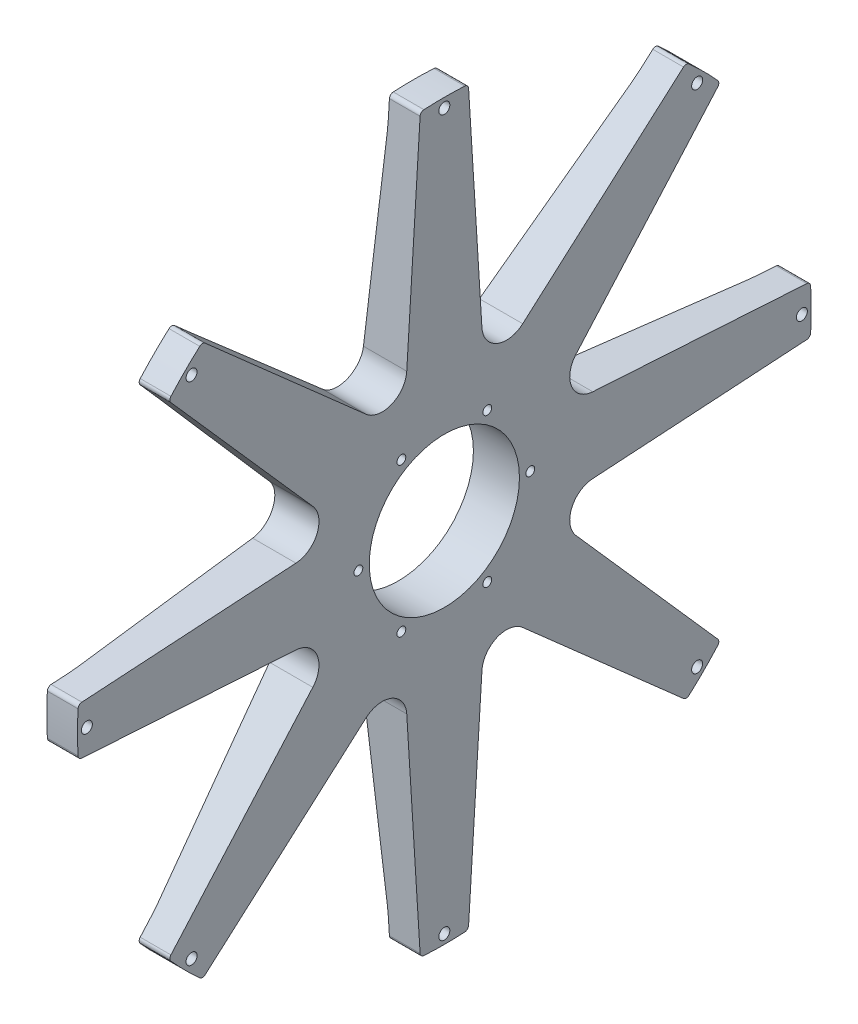
SolidWorks part; units mm, degrees
material "6061-T6 (SS)"
ref_plane "Front Plane" through (0, 0, 0) normal (1, 0, 0) x (0, 1, 0)
ref_plane "Top Plane" through (0, 0, 0) normal (0, 0, 1) x (0, 1, 0)
ref_plane "Right Plane" through (0, 0, 0) normal (0, 1, 0) x (-1, 0, 0)
sketch "Rim Base" plane through (1321.9127, 0, 0) normal (-1, 0, 0) x (0, -1, 0)
  line L0 (-601.9127, 917.067) -> (-621.8122, 869.0252) construction
  line L1 (-601.9127, 742.367) -> (-601.9127, 737.792)
  line L2 (-601.9127, 737.792) -> (-601.9127, 737.592) construction
  line L3 (-601.9127, 917.067) -> (-582.0132, 869.0252) construction
  line L4 (-601.9127, 917.067) -> (-601.9127, 742.367)
  line L5 (-621.8122, 869.0252) -> (-606.8221, 747.1987)
  line L6 (-601.9127, 742.367) -> (-589.9127, 742.367) construction
  line L7 (-607.2191, 747.1498) -> (-606.8221, 747.1987) construction
  line L8 (-601.9127, 917.067) -> (-601.9127, 969.067)
  line L9 (-590.064, 739.9415) -> (-582.0132, 869.0252)
  line L10 (-582.0132, 869.0252) -> (-587.2177, 738.1946) construction
  circle A0 centre (-601.9127, 742.367) radius 2.6892
  circle A1 centre (-601.9127, 742.367) radius 2.4892 construction
  circle A2 centre (-601.9127, 742.367) radius 4.575
  arc A3 (-616.6077, 738.1946) -> (-587.2177, 738.1946) centre (-601.9127, 917.067) ccw construction
  arc A4 (-616.6077, 738.1946) -> (-587.2177, 738.1946) centre (-601.9127, 917.067) ccw construction
  circle A5 centre (-601.9127, 1091.767) radius 2.4892 construction
  circle A6 centre (-601.9127, 1091.767) radius 2.4892
  circle A7 centre (-601.9127, 917.067) radius 36.7
  circle A8 centre (-601.9127, 917.067) radius 36.5 construction
  circle A9 centre (-601.9127, 917.067) radius 36.5 construction
  circle A10 centre (-601.9127, 917.067) radius 36.5
  circle A11 centre (-601.9127, 917.067) radius 52
  arc A12 (-557.9844, 944.8934) -> (-599.7785, 969.0232) centre (-601.9127, 917.067) ccw construction
  arc A13 (-606.8221, 747.1987) -> (-606.4872, 742.3024) centre (-651.8191, 741.662) cw
  arc A14 (-590.064, 739.9415) -> (-591.9489, 738.0691) centre (-592.0601, 740.066) cw
  arc A15 (-601.9127, 737.792) -> (-591.9489, 738.0691) centre (-601.9127, 917.067) ccw
  circle A16 centre (-638.2858, 938.067) radius 2.1527 construction
  circle A17 centre (-638.2858, 896.067) radius 2.1527 construction
  circle A18 centre (-601.9127, 875.067) radius 2.1526 construction
  circle A19 centre (-565.5396, 896.067) radius 2.1526 construction
  circle A20 centre (-565.5396, 938.067) radius 2.1527 construction
  circle A21 centre (-601.9127, 959.067) radius 2.1526 construction
  circle A22 centre (-638.2858, 938.067) radius 2.1526
  circle A23 centre (-638.2858, 896.067) radius 2.1526
  circle A24 centre (-601.9127, 875.067) radius 2.1526
  circle A25 centre (-565.5396, 896.067) radius 2.1526
  circle A26 centre (-565.5396, 938.067) radius 2.1526
  circle A27 centre (-601.9127, 959.067) radius 2.1526
  arc M9 (-592.0897, 747.351) -> (-611.7357, 747.351) centre (-601.9127, 917.067) cw
  dimension "D1" = 0.2
  dimension "D2" = 0.2
  dimension "D3" = 0.2
  dimension "D4" = 12
  dimension "D7" = 2
  dimension "D5" = 22.5
  dimension "D6" = 0.4
extrude "Boss-Extrude1" add sketch "Rim Base" along normal blind 22.5 contours A11 L4 M9 | L4 A11 L8 A7 | L1 A2 L4 A0 | L4 A2 M9 | L8 A27 | A26 | L4 A24 | A25 region at (1321.9127, 599.9388, 740.3931) region at (1321.9127, 593.7172, 808.6969) region at (1321.9127, 600.7499, 868.9906) region at (1321.9127, 600.9991, 875.067) region at (1321.9127, 600.9991, 959.067) region at (1321.9127, 565.5396, 896.067) region at (1321.9127, 565.5396, 938.067)
ref_axis "Axis1" through (1299.4127, 601.9127, 917.067) along (1, 0, 0)
ref_axis "Axis2" through (1299.4127, 601.9127, 742.367) along (1, 0, 0)
ref_plane "Plane1" through (0, 601.9127, 0) normal (0, 1, 0) x (1, 0, 0)
sketch "Sketch1" plane through (0, 601.9127, 0) normal (0, 1, 0) x (1, 0, 0)
  line L0 (1321.9127, -865.067) -> (1299.4127, -865.067)
  line L1 (1299.4127, -880.367) -> (1299.4127, -745.0562) construction
  line L2 (1299.4127, -880.367) -> (1299.4127, -745.0562)
  line L6 (1299.4127, -739.6778) -> (1299.4127, -745.0562) construction
  line L7 (1306.9127, -737.792) -> (1306.9127, -747.792)
  line L9 (1306.7337, -753.1409) -> (1299.5918, -859.718)
  line L12 (1299.4127, -739.6778) -> (1299.4127, -737.792) construction
  line L13 (1299.4127, -737.792) -> (1321.9127, -737.792) construction
  line L15 (1299.4127, -739.6778) -> (1299.4127, -745.0562)
  line L16 (1299.4127, -739.6778) -> (1299.4127, -737.792)
  line L17 (1299.4127, -737.792) -> (1321.9127, -737.792)
  line L18 (1321.9127, -739.6778) -> (1321.9127, -737.792) construction
  arc A0 (1306.9127, -747.792) -> (1306.7337, -753.1409) centre (1226.9127, -747.792) cw
  arc A1 (1299.5918, -859.718) -> (1299.4127, -865.067) centre (1379.4127, -865.067) ccw
  dimension "D3" = 80
  dimension "D1" = 15
  dimension "D2" = 10
revolve "Cut-Revolve1" cut sketch "Sketch1" angle 360 about axis through (1299.4127, 601.9127, 917.067) along (1, 0, 0) region at (1302.1425, 601.9127, 779.7321)
mirror "Mirror1" about plane through (1299.4127, 601.9127, 0) normal (0, -1, 0) of bodies 104
pattern_circular "CirPattern1" count 8 every 45 about axis through (1299.4127, 601.9127, 917.067) along (1, 0, 0) of bodies 113 104
combine bodies "Combine1" bodies to combine 113 106 107 108 109 110 111 112
extrude "Cut-Extrude1" cut sketch "Rim Base<4>" along normal through all contours L8 A27 | L8 A27 | A26 | A25 | L4 A24 | L4 A24 | A23 | A22 region at (1321.9127, 602.8263, 875.067) region at (1321.9127, 600.9991, 875.067) region at (1321.9127, 600.9991, 959.067) region at (1321.9127, 602.8263, 959.067) region at (1321.9127, 638.2858, 938.067) region at (1321.9127, 638.2858, 896.067) region at (1321.9127, 565.5396, 896.067) region at (1321.9127, 565.5396, 938.067)
sketch "Rim Base<4>" plane through (1321.9127, 0, 0) normal (-1, 0, 0) x (0, -1, 0) same geometry as "Rim Base"
fillet "Fillet2" radius 12 8 edges at (1310.6627, 582.0132, 965.1087) (1310.6627, 553.871, 936.9665) (1310.6627, 553.871, 897.1674) (1310.6627, 582.0132, 869.0252) (1310.6627, 621.8122, 869.0252) (1310.6627, 649.9544, 897.1674) (1310.6627, 649.9544, 936.9665) (1310.6627, 621.8122, 965.1087)
equation "\"tol\"= 0.2mm"
